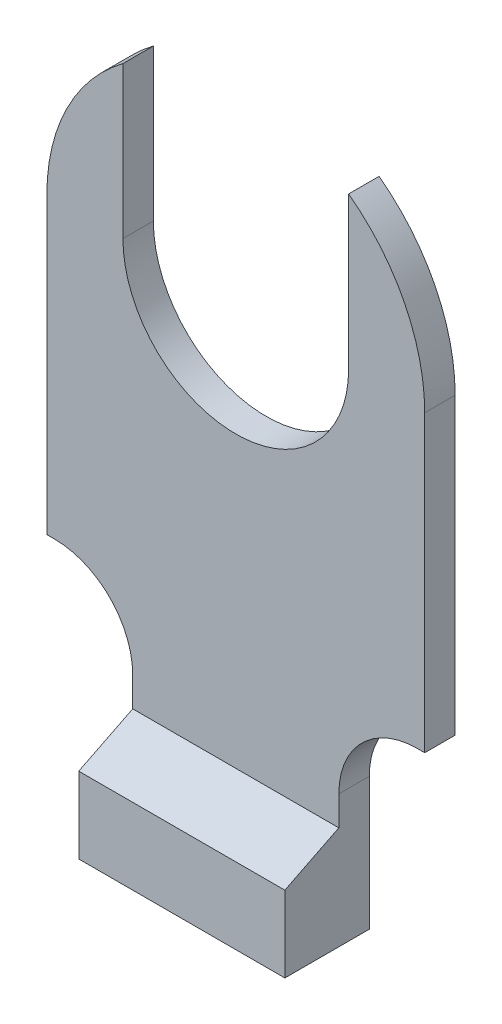
SolidWorks part; units mm, degrees
ref_plane "Спереди" through (0, 0, 0) normal (0, 0, 1) x (1, 0, 0)
ref_plane "Сверху" through (0, 0, 0) normal (0, 1, 0) x (1, 0, 0)
ref_plane "Справа" through (0, 0, 0) normal (1, 0, 0) x (0, 0, -1)
sketch "Эскиз1" plane through (0, 0, 0) normal (0, 0, 1) x (1, 0, 0)
  line L0 (-4.6, 0) -> (-4.6, 6.1749)
  line L1 (7.7, -20.6) -> (-7.7, -20.6)
  line L2 (7.7, -20.6) -> (7.7, 0)
  line L3 (4.6, 0) -> (4.6, 6.1749)
  line L4 (-7.7, -20.6) -> (-7.7, 0)
  arc A0 (7.7, 0) -> (4.6, 6.1749) centre (0, 0) ccw
  arc A1 (-4.6, 0) -> (4.6, 0) centre (0, 0) ccw
  arc A2 (-4.6, 6.1749) -> (-7.7, 0) centre (0, 0) ccw
  point P0 (0, 0)
  point P3 (0, -20.6)
  dimension "D3" = 9.2
  dimension "D1" = 20.6
  dimension "D2" = 15.4
extrude "Бобышка-Вытянуть1" add sketch "Эскиз1" along normal blind 1.24
sketch "Эскиз3" plane through (0, 0, 1.24) normal (0, 0, 1) x (1, 0, 0)
  line L0 (0, 0) -> (0, -20.6) construction
  line L1 (-7.7, -20.6) -> (-4.2, -20.6)
  line L2 (-7.7, -20.6) -> (-7.7, -12)
  line L3 (-7.7, -12) -> (-7.4, -12)
  line L4 (-4.2, -20.6) -> (-4.2, -15.2)
  line L5 (-7.7, -20.6) -> (7.7, -20.6) construction
  line L6 (4.2, -20.6) -> (4.2, -15.2)
  line L7 (7.7, -12) -> (7.4, -12)
  line L8 (7.7, -20.6) -> (7.7, -12)
  line L9 (7.7, -20.6) -> (4.2, -20.6)
  arc A0 (-4.2, -15.2) -> (-7.4, -12) centre (-7.4, -15.2) ccw
  arc A1 (4.2, -15.2) -> (7.4, -12) centre (7.4, -15.2) cw
  dimension "D3" = 3.2
  dimension "D1" = 4.2
  dimension "D2" = 8.6
extrude "Вырез-Вытянуть1" cut sketch "Эскиз3" against normal up to surface (1.24 mm away) up to face at (0, -4.0895, 0)
sketch "Эскиз4" plane through (0, 0, 1.24) normal (0, 0, 1) x (1, 0, 0)
  line L0 (4.2, -15.2) -> (4.2, -20.6) construction
  line L1 (-4.2, -20.6) -> (4.2, -20.6)
  line L2 (-4.2, -20.6) -> (-4.2, -17.6)
  line L3 (-4.2, -17.6) -> (4.2, -17.6)
  line L4 (4.2, -20.6) -> (4.2, -17.6)
  dimension "D1" = 3
extrude "Бобышка-Вытянуть2" add sketch "Эскиз4" along normal blind 2.2
chamfer "Фаска1" distance 1.2 distance2 2.4 1 edges at (0, -17.6, 1.24) first distance on face at (0, -7.4136, 1.24)
